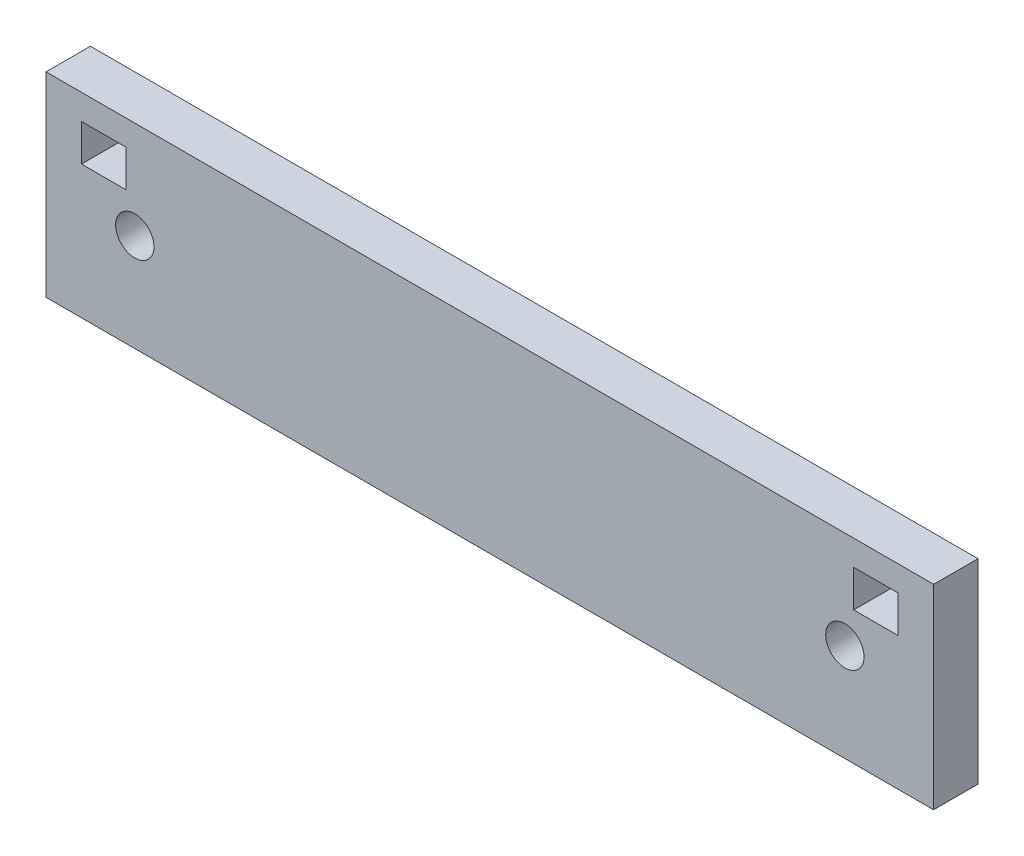
SolidWorks part; units mm, degrees
material "Beech"
ref_plane "Front Plane" through (0, 0, 0) normal (0, 0, 1) x (1, 0, 0)
ref_plane "Top Plane" through (0, 0, 0) normal (0, 1, 0) x (1, 0, 0)
ref_plane "Right Plane" through (0, 0, 0) normal (1, 0, 0) x (0, 0, -1)
sketch "Sketch1" plane through (0, 0, 0) normal (0, 0, 1) x (1, 0, 0)
  line L0 (14.605, 1.27) -> (13.0175, 1.27)
  line L1 (15.875, -3.4925) -> (-15.875, -3.4925)
  line L2 (15.875, -3.4925) -> (15.875, 3.4925)
  line L3 (15.875, 3.4925) -> (-15.875, 3.4925)
  line L4 (-15.875, -3.4925) -> (-15.875, 3.4925)
  line L5 (15.875, -3.4925) -> (-15.875, 3.4925) construction
  line L6 (15.875, 3.4925) -> (-15.875, -3.4925) construction
  line L7 (13.0175, 1.27) -> (13.0175, 2.5908)
  line L8 (13.0175, 2.5908) -> (14.605, 2.5908)
  line L9 (14.605, 2.5908) -> (14.605, 1.27)
  line L12 (0, -1000) -> (0, 49000) construction
  line L13 (-1000, 0) -> (49000, 0) construction
  line L37 (-14.605, 2.5908) -> (-14.605, 1.27)
  line L38 (-14.605, 1.27) -> (-13.0175, 1.27)
  line L39 (-13.0175, 1.27) -> (-13.0175, 2.5908)
  line L40 (-13.0175, 2.5908) -> (-14.605, 2.5908)
  circle A0 centre (-12.7, 0) radius 0.6858
  circle A1 centre (12.7, 0) radius 0.6858
  point P0 (0, 0)
  dimension "D6" = 12.7
  dimension "D7" = 1.3208
  dimension "D5" = 1.3716
  dimension "D1" = 6.985
  dimension "D2" = 31.75
  dimension "D3" = 1.27
  dimension "D4" = 0.9017
  dimension "D8" = 1.5875
extrude "Boss-Extrude1" add sketch "Sketch1" along normal blind 1.5875
